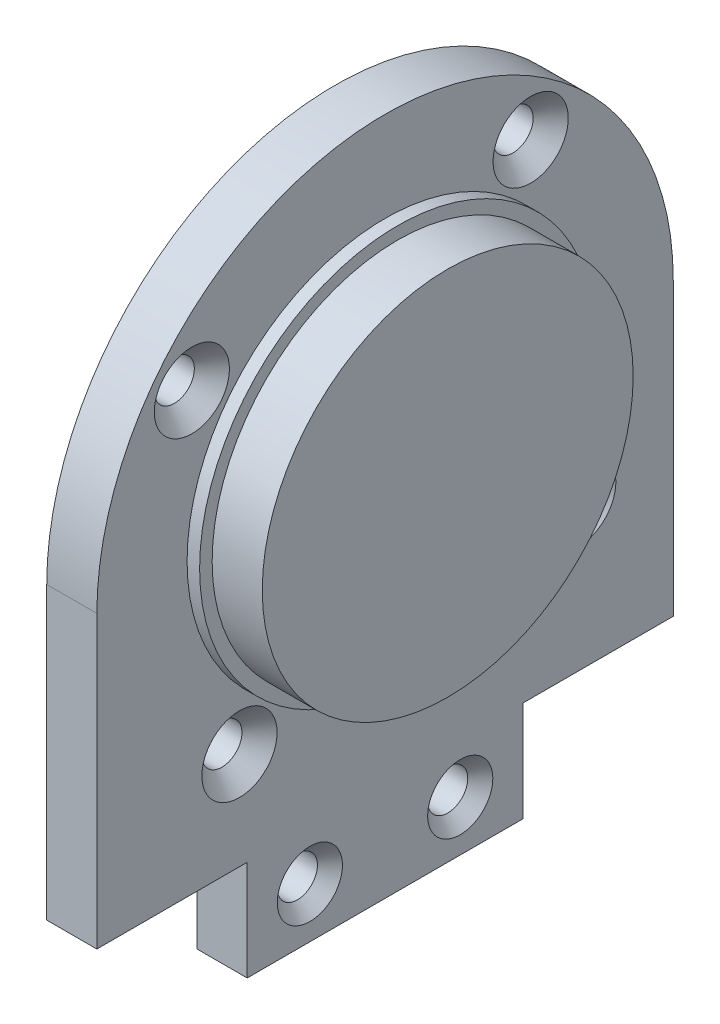
SolidWorks part; units mm, degrees
material "3d打印 35%"
ref_plane "前视基准面" through (0, 0, 0) normal (0, 0, 1) x (1, 0, 0)
ref_plane "上视基准面" through (0, 0, 0) normal (0, 1, 0) x (1, 0, 0)
ref_plane "右视基准面" through (0, 0, 0) normal (1, 0, 0) x (0, 0, -1)
other "Configuration Table"
sketch "草图1" plane through (0, 0, 0) normal (1, 0, 0) x (0, 0, -1)
  line L0 (0, 0) -> (-29.5495, 22.2672) construction
  line L1 (-23, 0) -> (-23, -23.2)
  line L2 (-23, -23.2) -> (23, -23.2)
  line L3 (23, -23.2) -> (23, 0)
  line L4 (-23, -23.2) -> (-23, -31.2)
  line L5 (-23, -31.2) -> (23, -31.2)
  line L6 (23, -31.2) -> (23, -23.2)
  line L7 (0, -23.2) -> (0, -31.2) construction
  line L8 (-6, -27.2) -> (6, -27.2) construction
  line L9 (-11, -27.2) -> (11, -27.2) construction
  line L10 (-11, -23.2) -> (-11, -31.2)
  line L11 (-11, -31.2) -> (11, -31.2)
  line L12 (11, -31.2) -> (11, -23.2)
  circle A0 centre (0, 0) radius 23
  circle A1 centre (0, 0) radius 19.25 construction
  circle A2 centre (-15.4201, 11.6199) radius 1.6
  circle A3 centre (11.6199, 15.4201) radius 1.6
  circle A4 centre (15.4201, -11.6199) radius 1.6
  circle A5 centre (-11.6199, -15.4201) radius 1.6
  circle A6 centre (6, -27.2) radius 1.6
  circle A7 centre (-6, -27.2) radius 1.6
  circle A8 centre (0, 0) radius 14.8
  point P16 (0, 0)
  point P25 (0, -27.2)
  point P30 (0, -27.2)
  dimension "D1" = 4
extrude "凸台-拉伸4" add sketch "草图1" along normal blind 4 contours A0 A5 A4 A3 A2 | A0 L1 L2 L3 region at (0, -23.0515, 0) region at (0, 22.3495, 0)
extrude "凸台-拉伸5" add sketch "草图1<6>" along normal blind 4 contours L5 L12 L2 L10 A7 A6 region at (0, -27.2, 0)
sketch "草图1<6>" plane through (0, 0, 0) normal (1, 0, 0) x (0, 0, -1) same geometry as "草图1"
chamfer "倒角1" distance 1.4 angle 45 4 edges at (4, -11.6199, -17.0201) (4, -15.4201, 10.0199) (4, 15.4201, -13.2199) (4, 11.6199, 13.8201)
chamfer "倒角2" distance 1 angle 45 1 edges at (4, -27.2, 4.4)
chamfer "倒角3" distance 1 angle 45 1 edges at (4, -27.2, -7.6)
extrude "凸台-拉伸6" add sketch "草图1<7>" along normal blind 9 contours A8 region at (0, 0, 0)
sketch "草图1<7>" plane through (0, 0, 0) normal (1, 0, 0) x (0, 0, -1) same geometry as "草图1"
sketch "草图2" plane through (4, 0, 0) normal (1, 0, 0) x (0, 0, -1)
  circle A0 centre (0, 0) radius 15.8
extrude "凸台-拉伸7" add sketch "草图2" along normal blind 1
